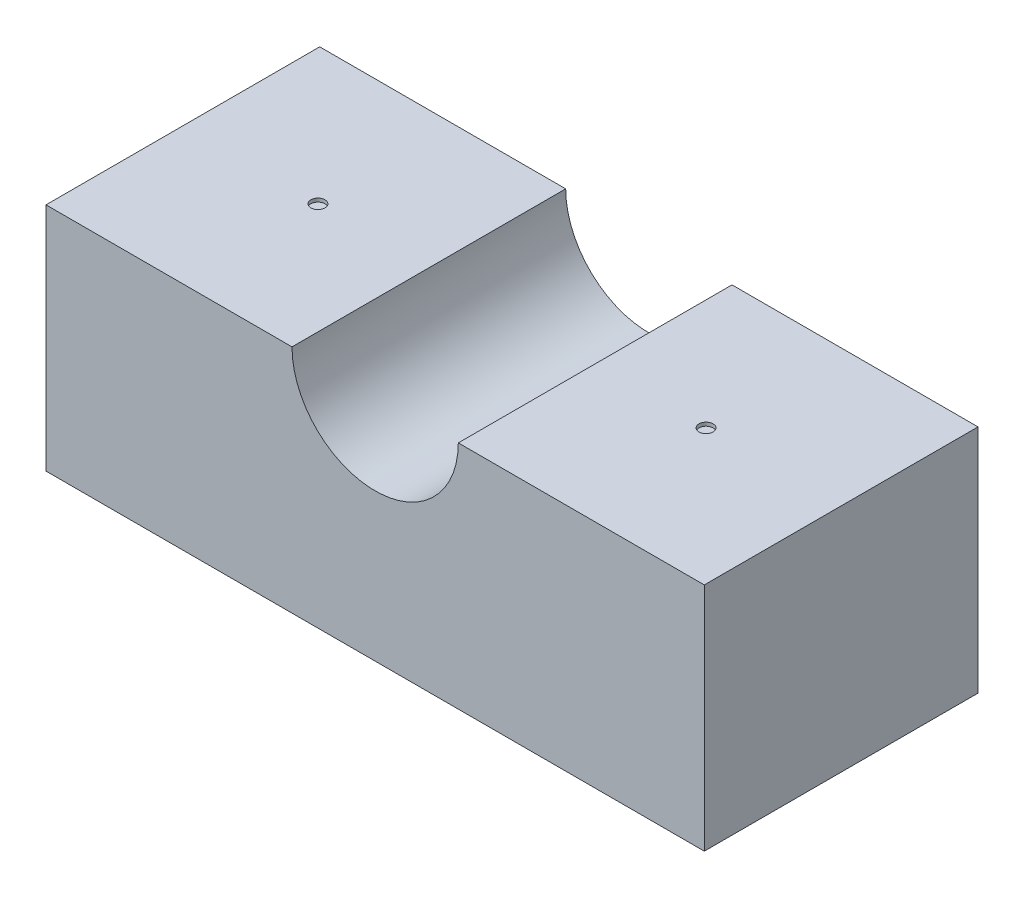
SolidWorks part; units mm, degrees
material "Custom Plastic"
ref_plane "Front Plane" through (0, 0, 0) normal (0, 0, 1) x (1, 0, 0)
ref_plane "Top Plane" through (0, 0, 0) normal (0, 1, 0) x (1, 0, 0)
ref_plane "Right Plane" through (0, 0, 0) normal (1, 0, 0) x (0, 0, -1)
sketch "Sketch2" plane through (0, 0, 0) normal (0, 1, 0) x (1, 0, 0)
  line L0 (-11.873, 4.9365) -> (11.873, 4.9365)
  line L1 (11.873, 4.9365) -> (11.873, -4.9365)
  line L2 (11.873, -4.9365) -> (-11.873, -4.9365)
  line L3 (-11.873, -4.9365) -> (-11.873, 4.9365)
  dimension "D1" = 11.873
  dimension "D2" = 4.9365
  dimension "D3" = 4.9365
  dimension "D4" = 11.873
extrude "Boss-Extrude1" add sketch "Sketch2" along normal blind 8.3185 contours L0 L1 L2 L3
sketch "Sketch3" plane through (0, 0, 4.9365) normal (0, 0, 1) x (1, 0, 0)
  line L0 (11.873, 8.3185) -> (-11.873, 8.3185) construction
  circle A0 centre (0, 8.3185) radius 2.9997
extrude "Cut-Extrude1" cut sketch "Sketch3" against normal through all contours A0
sketch "Sketch4" plane through (0, 8.3185, 0) normal (0, 1, 0) x (1, 0, 0)
  circle A0 centre (-7, 0) radius 0.254
  circle A1 centre (7, 0) radius 0.254
  point P4 (0, 0)
  point P7 (0, 0)
extrude "Cut-Extrude2" cut sketch "Sketch4" against normal blind 0.127
